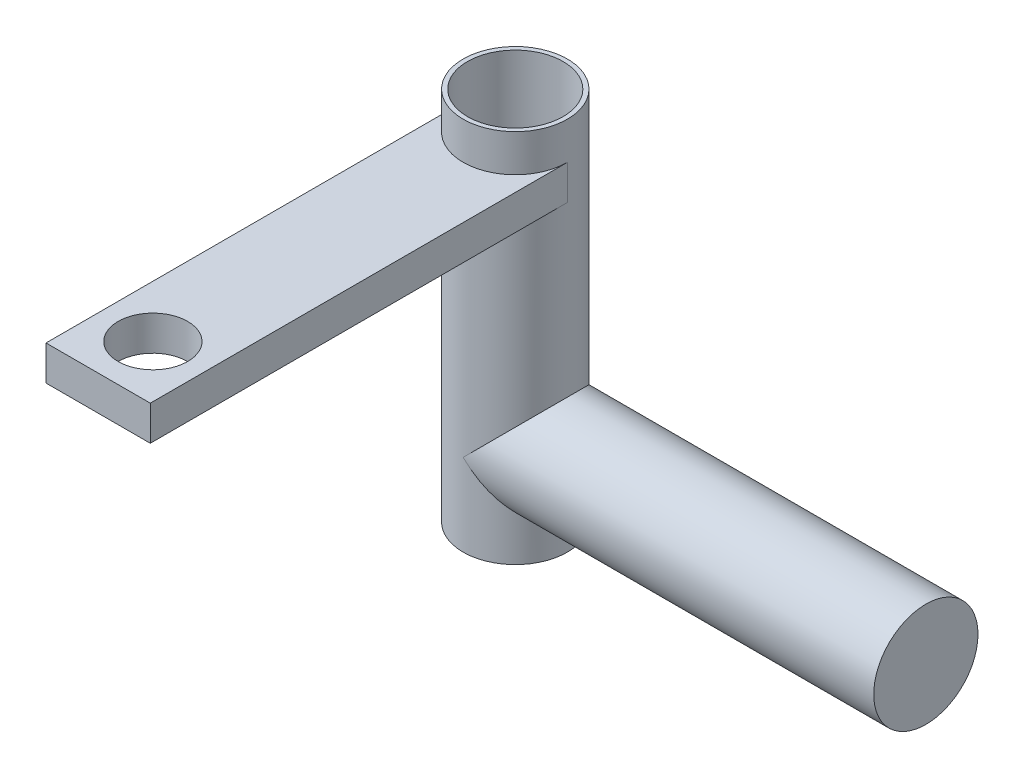
SolidWorks part; units mm, degrees
material "Alumina"
ref_plane "Front Plane" through (0, 0, 0) normal (0, 0, 1) x (1, 0, 0)
ref_plane "Top Plane" through (0, 0, 0) normal (0, 1, 0) x (1, 0, 0)
ref_plane "Right Plane" through (0, 0, 0) normal (1, 0, 0) x (0, 0, -1)
sketch "Sketch1" plane through (0, 0, 0) normal (0, 1, 0) x (1, 0, 0)
  circle A0 centre (0, 0) radius 9.525
  dimension "D1" = 19.05
extrude "Sleeve" add sketch "Sketch1" along normal blind 63.5 and the other way blind 5
sketch "Sketch2" plane through (0, 0, 0) normal (0, 0, 1) x (1, 0, 0)
  line L0 (0, -40.1638) -> (0, 40.1638) construction
  line L1 (9.525, 56.675) -> (-9.525, 56.675)
  line L2 (9.525, 56.675) -> (9.525, 50.325)
  line L3 (9.525, 50.325) -> (-9.525, 50.325)
  line L4 (-9.525, 56.675) -> (-9.525, 50.325)
  line L5 (9.525, 56.675) -> (-9.525, 50.325) construction
  line L6 (9.525, 50.325) -> (-9.525, 56.675) construction
  point P0 (0, 53.5)
  dimension "D2" = 19.05
  dimension "D3" = 53.5
extrude "Bracket" add sketch "Sketch2" along normal blind 76.2
sketch "Sketch4" plane through (0, 0, 0) normal (0, 1, 0) x (1, 0, 0)
  line L0 (0, -40.1638) -> (0, 40.1638) construction
  circle A0 centre (0, -66.2) radius 6.35
  dimension "D1" = 12.7
  dimension "D2" = 66.2
extrude "Bracket Hole" cut sketch "Sketch4" along normal through all
sketch "Sketch5" plane through (0, 0, 0) normal (1, 0, 0) x (0, 0, -1)
  line L0 (0, 27.94) -> (0, -27.94) construction
  circle A0 centre (0, 10) radius 9.525
  dimension "D2" = 19.05
  dimension "D1" = 10
extrude "Shaft" add sketch "Sketch5" along normal blind 75
sketch "Sketch6" plane through (0, 0, 0) normal (0, 1, 0) x (1, 0, 0)
  circle A0 centre (0, 0) radius 8.7313
  dimension "D1" = 17.4625
extrude "Sleeve Hole" cut sketch "Sketch6" along normal through all
equation "\"shaftDiameter\"= 25.4 / 4 * 3mm"
equation "\"shaftLength\"= 75mm"
equation "\"sleeveDiameter\"= 25.4 / 4 * 3mm"
equation "\"sleeveLength\"= 2.5 * 25.4mm"
equation "\"bracketLength\"= 3 * 25.4mm"
equation "\"D1@Sketch1\"=\"sleeveDiameter\""
equation "\"D1@Sleeve\" = \"sleeveLength\""
equation "\"D3@Sketch2\"=\"sleeveLength\"-10"
equation "\"D1@Bracket\" = \"bracketLength\""
equation "\"tieBarHoleDiameter\"= 25.4 / 2mm"
equation "\"D1@Sketch4\"=\"tieBarHoleDiameter\""
equation "\"D2@Sketch4\"=\"bracketLength\"-10"
equation "\"D2@Sketch5\"=\"shaftDiameter\""
equation "\"D1@Shaft\" = \"shaftLength\""
equation "\"sleeveWallThickness\"= 25.4 / 16"
equation "\"D1@Sketch6\"=\"sleeveDiameter\"-\"sleeveWallThickness\""
